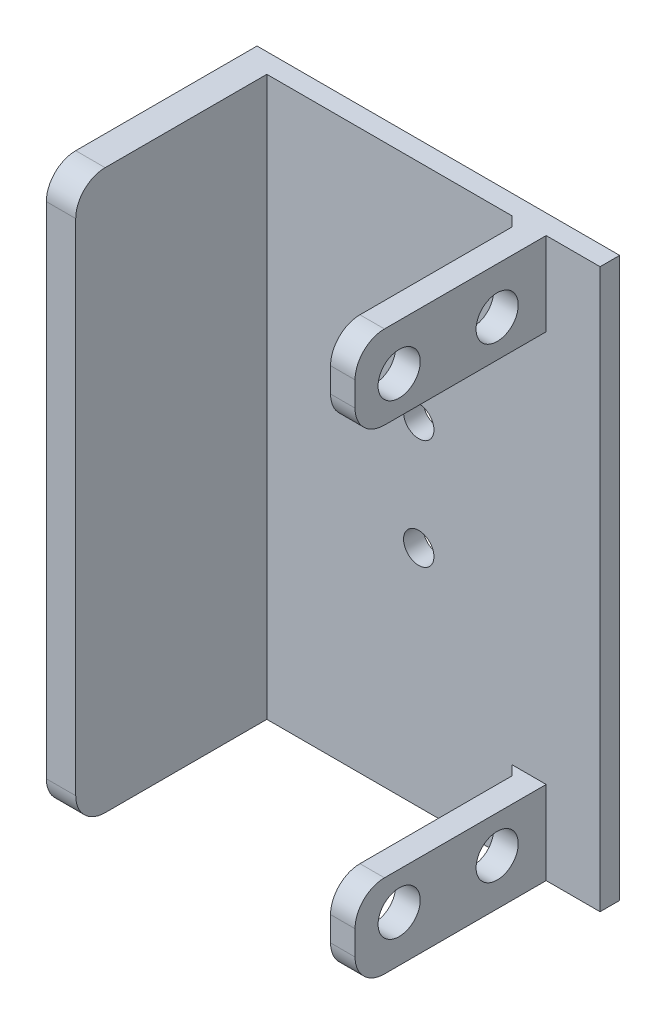
SolidWorks part; units mm, degrees
ref_plane "前视基准面" through (0, 0, 0) normal (0, 0, 1) x (1, 0, 0)
ref_plane "上视基准面" through (0, 0, 0) normal (0, 1, 0) x (1, 0, 0)
ref_plane "右视基准面" through (0, 0, 0) normal (1, 0, 0) x (0, 0, -1)
sketch "草图1" plane through (0, 0, 0) normal (0, 0, 1) x (1, 0, 0)
  line L1 (-18.5, 28.5) -> (18.5, 28.5)
  line L2 (-18.5, 28.5) -> (-18.5, -28.5)
  line L3 (-18.5, -28.5) -> (18.5, -28.5)
  line L4 (18.5, 28.5) -> (18.5, -28.5)
  line L5 (-18.5, 28.5) -> (18.5, -28.5) construction
  line L6 (-18.5, -28.5) -> (18.5, 28.5) construction
  point P0 (0, 0)
  dimension "D1" = 57
  dimension "D2" = 37
extrude "凸台-拉伸1" add sketch "草图1" along normal blind 2
sketch "草图2" plane through (0, 0, 2) normal (0, 0, 1) x (1, 0, 0)
  line L0 (-18.5, -28.5) -> (18.5, -28.5) construction
  line L1 (-18.5, 28.5) -> (-15.5, 28.5)
  line L2 (-18.5, 28.5) -> (-18.5, -28.5)
  line L3 (-18.5, -28.5) -> (-15.5, -28.5)
  line L4 (-15.5, 28.5) -> (-15.5, -28.5)
  dimension "D1" = 3
extrude "凸台-拉伸2" add sketch "草图2" along normal blind 19.5
sketch "草图3" plane through (0, 0, 2) normal (0, 0, 1) x (1, 0, 0)
  line L0 (13, -28.5) -> (13, -20)
  line L1 (-15.5, -28.5) -> (18.5, -28.5) construction
  line L2 (13, -20) -> (10.5, -20)
  line L3 (10.5, -20) -> (10.5, -28.5)
  line L4 (-15.5, -28.5) -> (-15.5, 28.5) construction
  line L5 (10.5, -28.5) -> (13, -28.5)
  line L6 (10.5, -20) -> (10.5, 20) construction
  line L7 (10.5, 20) -> (10.5, 28.5)
  line L8 (10.5, 28.5) -> (13, 28.5)
  line L9 (13, 28.5) -> (13, 20)
  line L10 (10.5, 20) -> (13, 20)
  dimension "D1" = 28.5
  dimension "D2" = 2.5
  dimension "D3" = 40
  dimension "D4" = 8.5
  dimension "D5" = 2.5
  dimension "D7" = 8.5
extrude "凸台-拉伸3" add sketch "草图3" along normal blind 19.5
sketch "草图4" plane through (0, 0, 2) normal (0, 0, 1) x (1, 0, 0)
  line L0 (0, 0) -> (0, -5.6)
  line L1 (0, 0) -> (-14.5, 0) construction
  circle A0 centre (0, -5.6) radius 1.55
  circle A1 centre (0, 5.6) radius 1.55
  dimension "D1" = 3.1
  dimension "D2" = 5.6
extrude "切除-拉伸1" cut sketch "草图4" against normal through all contours A1 | A0 region at (0, 5.6, 2)
sketch "草图6" plane through (-18.5, 0, 0) normal (-1, 0, 0) x (0, 0, 1)
  line L0 (21.5, -20) -> (2, -20) construction
  line L1 (21.5, -20) -> (2, -20) construction
  line L2 (11.5, -20) -> (11.5, -9.9) construction
  line L3 (21.5, 28.5) -> (21.5, -28.5) construction
  circle A0 centre (11.5, -9.9) radius 2.5
  dimension "D3" = 5
  dimension "D1" = 10.1
  dimension "D2" = 10
extrude "凸台-拉伸4" add sketch "草图6" along normal blind 7
sketch "草图7" plane through (13, 0, 0) normal (1, 0, 0) x (0, 0, -1)
  line L0 (-21.5, -28.5) -> (-21.5, -20) construction
  line L1 (0, 0) -> (-24.1864, 0) construction
  circle A0 centre (-17, -23.793) radius 2.15
  circle A1 centre (-7, -23.793) radius 2.15
  circle A2 centre (-7, 23.793) radius 2.15
  circle A3 centre (-17, 23.793) radius 2.15
  dimension "D1" = 4.5
  dimension "D2" = 4.3
  dimension "D3" = 10
extrude "切除-拉伸2" cut sketch "草图7" against normal blind 3
fillet "圆角1" radius 3 6 edges at (11.75, 28.5, 21.5) (11.75, -20, 21.5) (11.75, 20, 21.5) (11.75, -28.5, 21.5) (-17, -28.5, 21.5) (-17, 28.5, 21.5)
chamfer "倒角2" distance 1 angle 45 2 edges at (10.5, -24.25, 2) (10.5, 24.25, 2)
